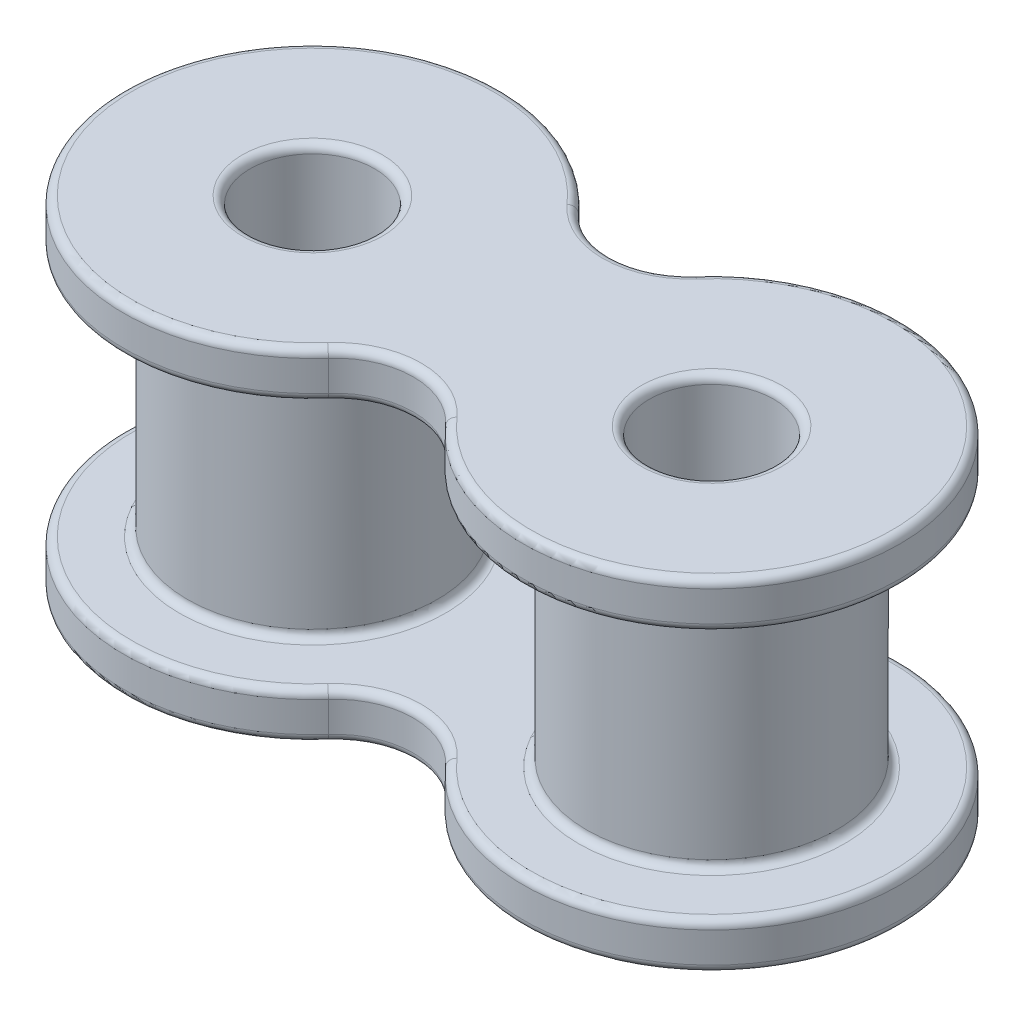
SolidWorks part; units mm, degrees
material "Alloy Steel"
ref_plane "X-Y Datum" through (0, 0, 0) normal (0, 0, 1) x (1, 0, 0)
ref_plane "X-Z Datum" through (0, 0, 0) normal (0, 1, 0) x (1, 0, 0)
ref_plane "Y-Z Datum" through (0, 0, 0) normal (1, 0, 0) x (0, 0, -1)
sketch "Sketch1" plane through (0, 0, 0) normal (0, 1, 0) x (1, 0, 0)
  line L0 (0, 9.8489) -> (0, -11.4215) construction
  line L1 (-12.6403, 0) -> (12.9549, 0) construction
  circle A0 centre (-6.35, 0) radius 1.9812
  arc A1 (-1.8654, 3.9776) -> (-1.8654, -3.9776) centre (-6.35, 0) ccw
  arc A2 (1.8654, 3.9776) -> (1.8654, -3.9776) centre (6.35, 0) cw
  circle A3 centre (6.35, 0) radius 1.9812
  arc A4 (-1.8654, 3.9776) -> (1.8654, 3.9776) centre (0, 5.6322) ccw
  arc A5 (-1.8654, -3.9776) -> (1.8654, -3.9776) centre (0, -5.6322) cw
  dimension "D1" = 11.9888
  dimension "D2" = 3.9624
  dimension "D4" = 2.4935
  dimension "D3" = 6.35
extrude "Boss-Extrude1" add sketch "Sketch1" along normal mid plane 1.4732
sketch "Sketch5" plane through (0, 0.7366, 0) normal (0, 1, 0) x (1, 0, 0)
  line L0 (0, -55) -> (0, 55) construction
  circle A0 centre (6.35, 0) radius 1.9812 construction
  circle A1 centre (6.35, 0) radius 1.9812
  circle A2 centre (-6.35, 0) radius 1.9812
  circle A3 centre (6.35, 0) radius 3.9751
  circle A4 centre (-6.35, 0) radius 3.9751
  dimension "D1" = 7.9502
extrude "Boss-Extrude2" add sketch "Sketch5" along normal blind 7.9248
fillet "Fillet" radius 0.254 12 edges at (0, 0.7366, -3.1387) (12.3444, 0.7366, 0) (0, 0.7366, 3.1387) (-12.3444, -0.7366, 0) (0, -0.7366, -3.1387) (-12.3444, 0.7366, 0) (6.35, -0.7366, -1.9812) (-6.35, -0.7366, 1.9812) (0, -0.7366, 3.1387) (12.3444, -0.7366, 0) (6.35, 0.7366, 3.9751) (-6.35, 0.7366, -3.9751)
ref_plane "Center Plane" through (0, 4.699, 0) normal (0, 1, 0) x (1, 0, 0)
mirror "Mirror2" about plane through (0, 4.699, 0) normal (0, 1, 0) of "Fillet", "Boss-Extrude1"
ref_plane "Plane1" through (0, 4.699, 0) normal (0, 1, 0) x (1, 0, 0)
ref_plane "Plane2" through (0, 4.699, 0) normal (0, 1, 0) x (1, 0, 0)
